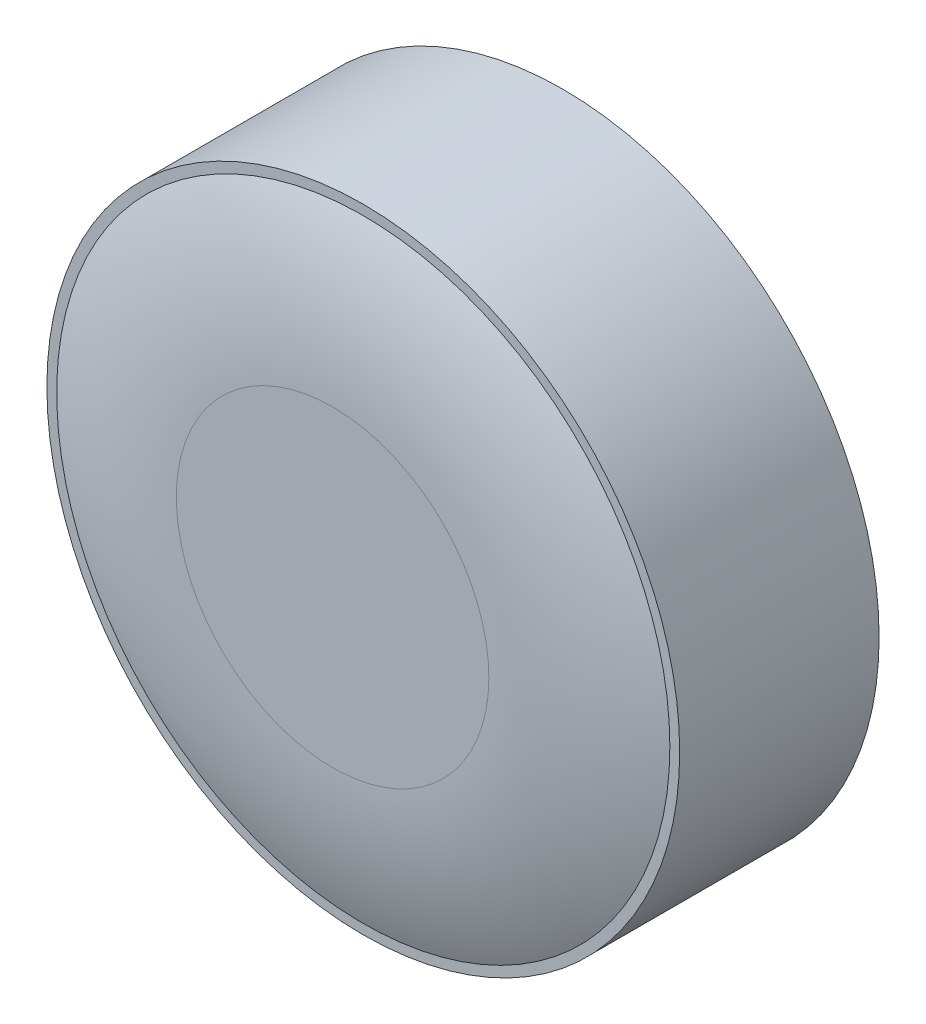
SolidWorks part; units mm, degrees
ref_plane "Front Plane" through (0, 0, 0) normal (0, 0, 1) x (1, 0, 0)
ref_plane "Top Plane" through (0, 0, 0) normal (0, 1, 0) x (1, 0, 0)
ref_plane "Right Plane" through (0, 0, 0) normal (1, 0, 0) x (0, 0, -1)
sketch "Sketch1" plane through (0, 0, 0) normal (0, 0, 1) x (1, 0, 0)
  circle A0 centre (0, 0) radius 8.25
  circle A1 centre (0, 0) radius 7.994
  point P5 (0, 0)
  dimension "D1" = 16.5
extrude "Boss-Extrude1" add sketch "Sketch1" along normal blind 5.2 contours A0 A1 | A0 region at (-8.0167, 0, 0)
extrude "Boss-Extrude3" add sketch "Sketch1<4>" along normal blind 6 contours A1 region at (0, 0, 0)
sketch "Sketch1<4>" plane through (0, 0, 0) normal (0, 0, 1) x (1, 0, 0) same geometry as "Sketch1"
fillet "Fillet1" radius 10 1 edges at (7.994, 0, 6)
ref_axis "Axis1" through (0, 0, 0) along (0, 0, -1)
